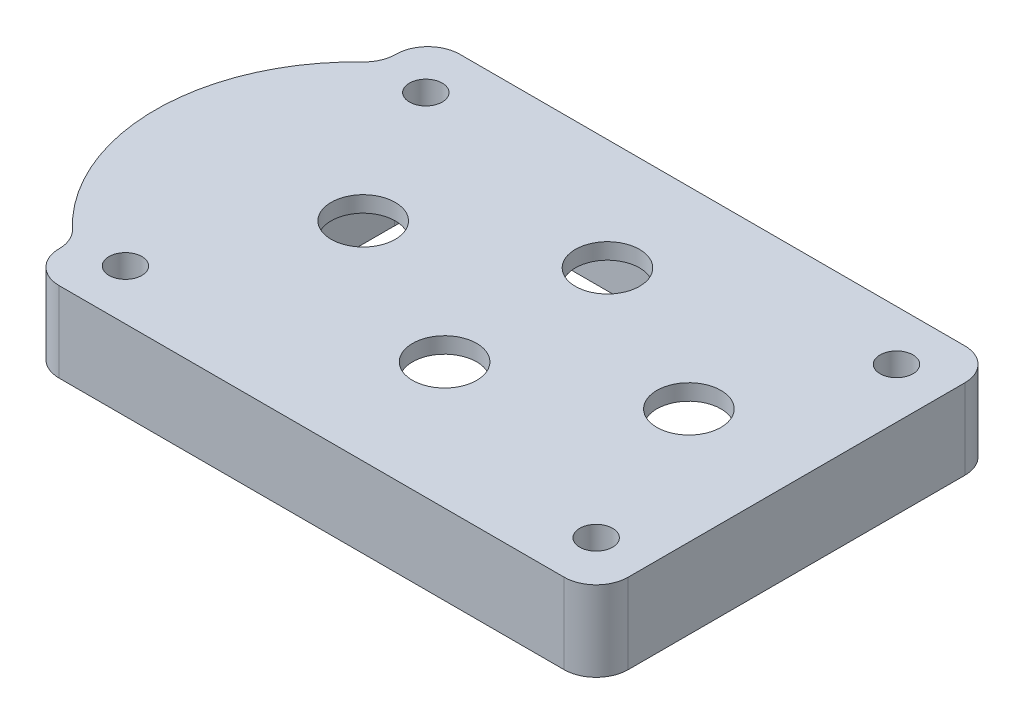
SolidWorks part; units mm, degrees
ref_plane "Front Plane" through (0, 0, 0) normal (0, 0, 1) x (1, 0, 0)
ref_plane "Top Plane" through (0, 0, 0) normal (0, 1, 0) x (1, 0, 0)
ref_plane "Right Plane" through (0, 0, 0) normal (1, 0, 0) x (0, 0, -1)
sketch "Sketch1" plane through (0, 0, 0) normal (0, 1, 0) x (1, 0, 0)
  line L1 (-20, -12.5) -> (20, -12.5)
  line L2 (-20, -12.5) -> (-20, 12.5)
  line L3 (-20, 12.5) -> (20, 12.5)
  line L4 (20, -12.5) -> (20, 12.5)
  line L5 (-20, -12.5) -> (20, 12.5) construction
  line L6 (-20, 12.5) -> (20, -12.5) construction
  point P0 (0, 0)
  dimension "D1" = 25
  dimension "D2" = 40
extrude "Boss-Extrude1" add sketch "Sketch1" along normal blind 5
sketch "Sketch2" plane through (0, 5, 0) normal (0, 1, 0) x (1, 0, 0)
  line L0 (0, 0) -> (-20, 0) construction
  line L1 (-20, 12.5) -> (-20, -12.5) construction
  line L6 (20, -12.5) -> (20, 12.5)
  line L7 (20, 12.5) -> (-20, 12.5)
  line L8 (-20, 12.5) -> (-20, -12.5)
  line L9 (-20, -12.5) -> (20, -12.5)
  line L10 (20, -12.5) -> (20, 12.5)
  line L11 (20, 12.5) -> (-20, 12.5)
  line L12 (-20, 12.5) -> (-20, -12.5)
  line L13 (-20, -12.5) -> (20, -12.5)
  circle A0 centre (-7.5, 0) radius 12.5
  point P5 (-7.5, 0)
  line M8 (-20, 12.5) -> (-20, -12.5)
  line M9 (-20, -12.5) -> (20, -12.5)
  dimension "D1" = 12.5
  dimension "D2" = 0
extrude "Cut-Extrude1" cut sketch "Sketch2" against normal through all contours A0 L11 M8 | A0 L12 M9 region at (-17.2079, 5, 9.7079) region at (-17.2079, 5, -9.7079)
sketch "Sketch4" plane through (0, 5, 0) normal (0, 1, 0) x (1, 0, 0)
  line L1 (-7.5, -12.5) -> (-15.5, -12.5)
  line L2 (-7.5, -12.5) -> (-7.5, 12.5)
  line L3 (-7.5, 12.5) -> (-15.5, 12.5)
  line L4 (-15.5, -12.5) -> (-15.5, 12.5)
  dimension "D1" = 8
extrude "Boss-Extrude2" add sketch "Sketch4" against normal through all
fillet "Fillet1" radius 2 6 edges at (20, 2.5, 12.5) (20, 2.5, -12.5) (-15.5, 2.5, -12.5) (-15.5, 2.5, 12.5) (-15.5, 2.5, -9.6047) (-15.5, 2.5, 9.6047)
sketch "Sketch5" plane through (0, 5, 0) normal (0, 1, 0) x (1, 0, 0)
  line L0 (16.87, 9.37) -> (-12.496, 9.37) construction
  line L1 (-12.496, -9.37) -> (16.87, -9.37) construction
  line L2 (16.87, -9.37) -> (16.87, 9.37) construction
  line L3 (18, 12.5) -> (-13.5, 12.5)
  line L4 (-13.5, -12.5) -> (18, -12.5)
  line L5 (20, -10.5) -> (20, 10.5)
  line L6 (18, 12.5) -> (-13.5, 12.5)
  line L7 (-13.5, -12.5) -> (18, -12.5)
  line L8 (20, -10.5) -> (20, 10.5)
  arc A0 (-12.496, 9.37) -> (-12.496, 9.37) centre (-12.496, 9.37) ccw
  arc A1 (-13.9621, 6.7852) -> (-12.496, 9.37) centre (-17.5, 10.5) ccw construction
  arc A2 (-13.9621, 6.7852) -> (-13.9621, -6.7852) centre (-7.5, 0) ccw construction
  arc A3 (-12.496, -9.37) -> (-13.9621, -6.7852) centre (-17.5, -10.5) ccw construction
  arc A4 (-12.496, -9.37) -> (-12.496, -9.37) centre (-12.496, -9.37) ccw
  arc A5 (16.87, -9.37) -> (16.87, -9.37) centre (16.87, -9.37) ccw
  arc A6 (16.87, 9.37) -> (16.87, 9.37) centre (16.87, 9.37) ccw
  arc A7 (-13.5, 12.5) -> (-15.5, 10.5) centre (-13.5, 10.5) ccw
  arc A8 (-16.1207, 9.0517) -> (-15.5, 10.5) centre (-17.5, 10.5) ccw
  arc A9 (-16.1207, 9.0517) -> (-16.1207, -9.0517) centre (-7.5, 0) ccw
  arc A10 (-15.5, -10.5) -> (-16.1207, -9.0517) centre (-17.5, -10.5) ccw
  arc A11 (-15.5, -10.5) -> (-13.5, -12.5) centre (-13.5, -10.5) ccw
  arc A12 (18, -12.5) -> (20, -10.5) centre (18, -10.5) ccw
  arc A13 (20, 10.5) -> (18, 12.5) centre (18, 10.5) ccw
  arc A14 (-13.5, 12.5) -> (-15.5, 10.5) centre (-13.5, 10.5) ccw
  arc A15 (-16.1207, 9.0517) -> (-15.5, 10.5) centre (-17.5, 10.5) ccw
  arc A16 (-16.1207, 9.0517) -> (-16.1207, -9.0517) centre (-7.5, 0) ccw
  arc A17 (-15.5, -10.5) -> (-16.1207, -9.0517) centre (-17.5, -10.5) ccw
  arc A18 (-15.5, -10.5) -> (-13.5, -12.5) centre (-13.5, -10.5) ccw
  arc A19 (18, -12.5) -> (20, -10.5) centre (18, -10.5) ccw
  arc A20 (20, 10.5) -> (18, 12.5) centre (18, 10.5) ccw
  circle A21 centre (16.87, 9.37) radius 1.025
  circle A22 centre (16.87, -9.37) radius 1.025
  circle A23 centre (-12.496, -9.37) radius 1.025
  circle A24 centre (-12.496, 9.37) radius 1.025
  dimension "D3" = 2.05
  dimension "D4" = 2.05
  dimension "D5" = 2.05
  dimension "D6" = 2.05
  dimension "D1" = 0
  dimension "D2" = 3.13
extrude "Cut-Extrude2" cut sketch "Sketch5" against normal through all contours A24 | A23 | A21 | A22 region at (16.87, 5, -9.37) region at (16.87, 5, 9.37) region at (-12.496, 5, 9.37) region at (-12.496, 5, -9.37)
sketch "Sketch3" [suppressed] plane through (0, 0, 0) normal (0, -1, 0) x (1, 0, 0)
  line L0 (20, 0) -> (-20, 0) construction
  line L1 (20, 10.5) -> (20, -10.5) construction
  line L2 (0, -7.8582) -> (0, 7.8582)
  arc A0 (-16.1207, 9.0517) -> (-16.1207, -9.0517) centre (-7.5, 0) ccw construction
  circle A1 centre (-1.27, 0) radius 0.5
  circle A2 centre (-3.81, 0) radius 0.5
  circle A3 centre (-6.35, 0) radius 0.5
  circle A4 centre (-3.81, 2.54) radius 0.5
  circle A5 centre (-6.35, 2.54) radius 0.5
  circle A6 centre (-3.81, 5.08) radius 0.5
  circle A7 centre (-6.35, 5.08) radius 0.5
  circle A8 centre (-1.27, 2.54) radius 0.5
  circle A9 centre (-1.27, 5.08) radius 0.5
  circle A10 centre (1.27, 0) radius 0.5
  circle A11 centre (3.81, 0) radius 0.5
  circle A12 centre (6.35, 0) radius 0.5
  circle A13 centre (6.35, 2.54) radius 0.5
  circle A14 centre (3.81, 2.54) radius 0.5
  circle A15 centre (1.27, 2.54) radius 0.5
  circle A16 centre (1.27, 5.08) radius 0.5
  circle A17 centre (3.81, 5.08) radius 0.5
  circle A18 centre (6.35, 5.08) radius 0.5
  circle A19 centre (-6.35, -2.54) radius 0.5
  circle A20 centre (-6.35, -5.08) radius 0.5
  circle A21 centre (-3.81, -5.08) radius 0.5
  circle A22 centre (-1.27, -5.08) radius 0.5
  circle A23 centre (1.27, -5.08) radius 0.5
  circle A24 centre (3.81, -5.08) radius 0.5
  circle A25 centre (6.35, -5.08) radius 0.5
  circle A26 centre (6.35, -2.54) radius 0.5
  circle A27 centre (1.27, -2.54) radius 0.5
  circle A28 centre (-3.81, -2.54) radius 0.5
  circle A29 centre (-1.27, -2.54) radius 0.5
  circle A30 centre (3.81, -2.54) radius 0.5
  point P29 (0, 0)
  dimension "D1" = 1.27
  dimension "D2" = 1
  dimension "D3" = 3
  dimension "D4" = 3
sketch "Sketch6" plane through (0, 0, 0) normal (0, -1, 0) x (1, 0, 0)
  line L0 (3.9107, -0.485) -> (1.3707, -0.485) construction
  line L3 (-13.5, -12.5) -> (18, -12.5)
  line L4 (18, 12.5) -> (-13.5, 12.5)
  line L5 (20, -10.5) -> (20, 10.5)
  line L6 (-13.5, -12.5) -> (18, -12.5) construction
  line L7 (18, 12.5) -> (-13.5, 12.5) construction
  line L8 (20, -10.5) -> (20, 10.5) construction
  line L9 (-13.5, -12.5) -> (18, -12.5) construction
  line L11 (2.6407, -2.1673) -> (2.6407, 1.1973) construction
  line L12 (14.0707, -0.485) -> (11.5307, -0.485) construction
  line L13 (3.9107, -5.565) -> (1.3707, -5.565) construction
  circle A0 centre (-7.5193, -0.485) radius 2
  circle A1 centre (2.6407, 4.595) radius 2
  circle A4 centre (3.9107, -0.485) radius 0.5 construction
  circle A5 centre (3.9107, -0.485) radius 0.5 construction
  circle A6 centre (1.3707, -0.485) radius 0.5 construction
  arc A7 (-15.5, -10.5) -> (-13.5, -12.5) centre (-13.5, -10.5) ccw
  arc A8 (-15.5, -10.5) -> (-16.1207, -9.0517) centre (-17.5, -10.5) ccw
  arc A9 (-16.1207, 9.0517) -> (-16.1207, -9.0517) centre (-7.5, 0) ccw
  arc A10 (-16.1207, 9.0517) -> (-15.5, 10.5) centre (-17.5, 10.5) ccw
  arc A11 (-13.5, 12.5) -> (-15.5, 10.5) centre (-13.5, 10.5) ccw
  arc A12 (20, 10.5) -> (18, 12.5) centre (18, 10.5) ccw
  arc A13 (18, -12.5) -> (20, -10.5) centre (18, -10.5) ccw
  arc A14 (-15.5, -10.5) -> (-13.5, -12.5) centre (-13.5, -10.5) ccw construction
  arc A15 (-15.5, -10.5) -> (-16.1207, -9.0517) centre (-17.5, -10.5) ccw construction
  arc A16 (-16.1207, 9.0517) -> (-16.1207, -9.0517) centre (-7.5, 0) ccw construction
  arc A17 (-16.1207, 9.0517) -> (-15.5, 10.5) centre (-17.5, 10.5) ccw construction
  arc A18 (-13.5, 12.5) -> (-15.5, 10.5) centre (-13.5, 10.5) ccw construction
  arc A19 (20, 10.5) -> (18, 12.5) centre (18, 10.5) ccw construction
  arc A20 (18, -12.5) -> (20, -10.5) centre (18, -10.5) ccw construction
  circle A21 centre (1.3707, -0.485) radius 0.5 construction
  circle A22 centre (14.0707, -0.485) radius 0.5 construction
  circle A23 centre (14.0707, -0.485) radius 0.5 construction
  circle A24 centre (11.5307, -0.485) radius 0.5 construction
  circle A25 centre (11.5307, -0.485) radius 0.5 construction
  circle A26 centre (1.3707, -5.565) radius 0.5 construction
  circle A27 centre (1.3707, -5.565) radius 0.5 construction
  circle A28 centre (3.9107, -5.565) radius 0.5 construction
  circle A29 centre (3.9107, -5.565) radius 0.5 construction
  circle A30 centre (12.8007, -0.485) radius 2
  circle A31 centre (2.6407, -5.565) radius 2
  point P26 (2.6407, -0.485)
  dimension "D2" = 4
  dimension "D3" = 4
  dimension "D1" = 0
extrude "Cut-Extrude3" cut sketch "Sketch6" against normal through all contours A0 | A1 | A30 | A31 region at (-7.5193, 0, -0.485) region at (2.6407, 0, 4.595) region at (12.8007, 0, -0.485) region at (2.6407, 0, -5.565)
sketch "Sketch7" plane through (0, 0, 0) normal (0, -1, 0) x (1, 0, 0)
  line L0 (2.6407, 4.595) -> (2.6407, -5.565) construction
  line L1 (-11.2693, -6.19) -> (-11.2693, 5.22)
  line L2 (-7.5193, -5.565) -> (12.8007, -5.565) construction
  line L3 (-13.5, -12.5) -> (18, -12.5)
  line L4 (20, -10.5) -> (20, 10.5)
  line L5 (18, 12.5) -> (-13.5, 12.5)
  line L6 (-13.5, -12.5) -> (18, -12.5)
  line L7 (20, -10.5) -> (20, 10.5)
  line L8 (18, 12.5) -> (-13.5, 12.5)
  line L9 (-7.5193, -5.565) -> (-7.5193, 4.595) construction
  line L10 (-7.5193, 4.595) -> (12.8007, 4.595) construction
  line L11 (12.8007, -5.565) -> (12.8007, 4.595) construction
  line L12 (-7.5193, -5.565) -> (12.8007, 4.595) construction
  line L13 (-7.5193, 4.595) -> (12.8007, -5.565) construction
  line L14 (-8.1443, 8.345) -> (13.4257, 8.345)
  line L15 (16.5507, -6.19) -> (16.5507, 5.22)
  line L16 (-8.1443, -9.315) -> (13.4257, -9.315)
  line L17 (16.5507, -9.315) -> (16.5507, 8.345) construction
  line L18 (-11.2693, 8.345) -> (16.5507, 8.345) construction
  line L19 (-11.2693, -9.315) -> (16.5507, -9.315) construction
  line L20 (-11.2693, -9.315) -> (-11.2693, 8.345) construction
  circle A0 centre (2.6407, 4.595) radius 2 construction
  circle A1 centre (2.6407, 4.595) radius 2 construction
  circle A2 centre (2.6407, -5.565) radius 2 construction
  circle A3 centre (2.6407, -5.565) radius 2 construction
  circle A4 centre (-7.5193, -0.485) radius 2 construction
  circle A5 centre (-7.5193, -0.485) radius 2 construction
  circle A6 centre (12.8007, -0.485) radius 2 construction
  arc A7 (-16.1207, 9.0517) -> (-16.1207, -9.0517) centre (-7.5, 0) ccw
  arc A8 (-15.5, -10.5) -> (-16.1207, -9.0517) centre (-17.5, -10.5) ccw
  arc A9 (-15.5, -10.5) -> (-13.5, -12.5) centre (-13.5, -10.5) ccw
  arc A10 (18, -12.5) -> (20, -10.5) centre (18, -10.5) ccw
  arc A11 (20, 10.5) -> (18, 12.5) centre (18, 10.5) ccw
  arc A12 (-13.5, 12.5) -> (-15.5, 10.5) centre (-13.5, 10.5) ccw
  arc A13 (-16.1207, 9.0517) -> (-15.5, 10.5) centre (-17.5, 10.5) ccw
  arc A14 (-16.1207, 9.0517) -> (-16.1207, -9.0517) centre (-7.5, 0) ccw
  arc A15 (-15.5, -10.5) -> (-16.1207, -9.0517) centre (-17.5, -10.5) ccw
  arc A16 (-15.5, -10.5) -> (-13.5, -12.5) centre (-13.5, -10.5) ccw
  arc A17 (18, -12.5) -> (20, -10.5) centre (18, -10.5) ccw
  arc A18 (20, 10.5) -> (18, 12.5) centre (18, 10.5) ccw
  arc A19 (-13.5, 12.5) -> (-15.5, 10.5) centre (-13.5, 10.5) ccw
  arc A20 (-16.1207, 9.0517) -> (-15.5, 10.5) centre (-17.5, 10.5) ccw
  circle A21 centre (12.8007, -0.485) radius 2 construction
  arc A22 (16.5507, 5.22) -> (13.4257, 8.345) centre (13.4257, 5.22) ccw
  arc A23 (16.5507, -6.19) -> (13.4257, -9.315) centre (13.4257, -6.19) cw
  arc A24 (-8.1443, -9.315) -> (-11.2693, -6.19) centre (-8.1443, -6.19) cw
  arc A25 (-8.1443, 8.345) -> (-11.2693, 5.22) centre (-8.1443, 5.22) ccw
  point P29 (2.6407, -0.485)
  dimension "D3" = 3.125
  dimension "D1" = 0
  dimension "D2" = 3.75
extrude "Cut-Extrude4" cut sketch "Sketch7" against normal blind 4 contours L1 A24 L16 A23 L15 A22 L14 A25
ref_point "Point1"
